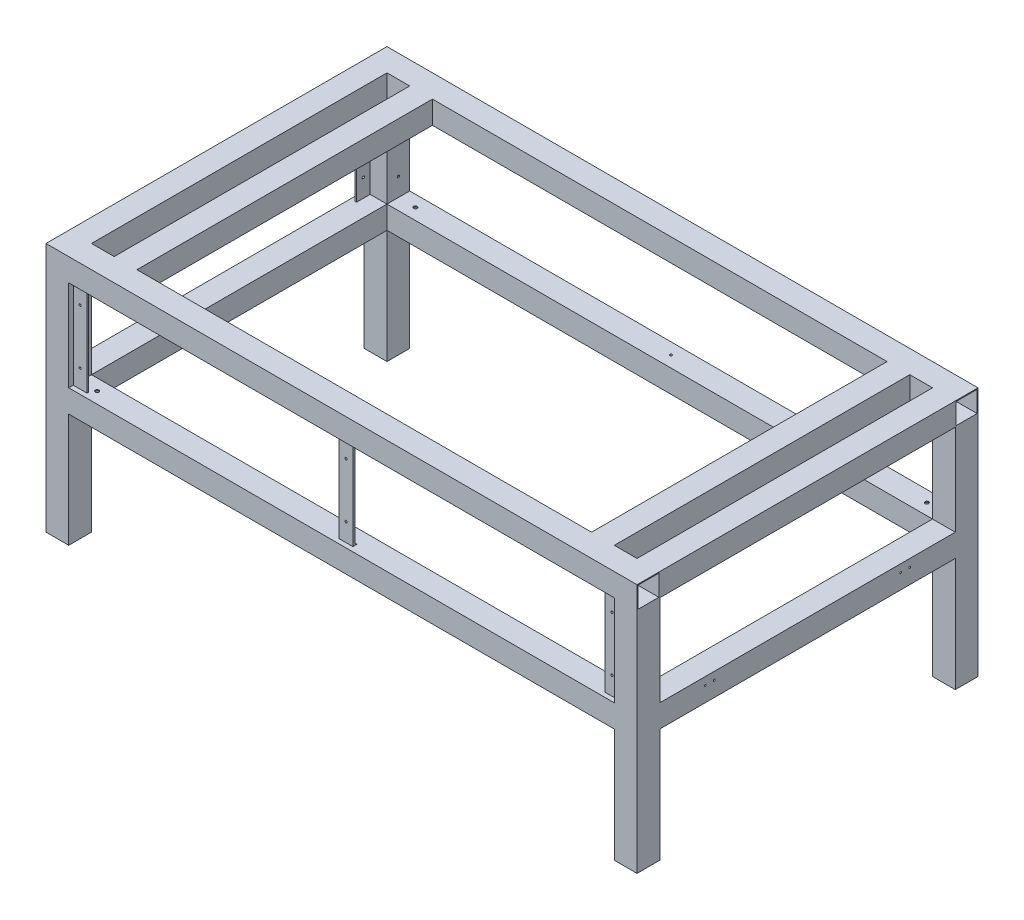
SolidWorks part; units mm, degrees
ref_plane "Plan de face" through (0, 0, 0) normal (0, 0, 1) x (1, 0, 0)
ref_plane "Plan de dessus" through (0, 0, 0) normal (0, 1, 0) x (1, 0, 0)
ref_plane "Plan de droite" through (0, 0, 0) normal (1, 0, 0) x (0, 0, -1)
sketch "Esquisse1" plane through (0, 0, 0) normal (0, 1, 0) x (1, 0, 0)
  line L1 (0, 0) -> (1300, 0)
  line L2 (0, 0) -> (0, 750)
  line L3 (0, 750) -> (1300, 750)
  line L4 (1300, 0) -> (1300, 750)
  line L5 (50, 700) -> (1250, 700)
  line L6 (50, 700) -> (50, 50)
  line L7 (50, 50) -> (1250, 50)
  line L8 (1250, 700) -> (1250, 50)
  dimension "D1" = 1300
  dimension "D2" = 750
  dimension "D3" = 50
  dimension "D4" = 50
  dimension "D5" = 50
  dimension "D6" = 50
extrude "Boss.-Extru.1" add sketch "Esquisse1" against normal blind 550
sketch "Esquisse2" plane through (0, 0, 0) normal (0, 0, 1) x (1, 0, 0)
  line L0 (0, 0) -> (1300, 0) construction
  line L1 (50, -50) -> (1250, -50)
  line L2 (50, -50) -> (50, -250)
  line L3 (50, -250) -> (1250, -250)
  line L4 (1250, -50) -> (1250, -250)
  line L5 (50, -300) -> (1250, -300)
  line L6 (50, -300) -> (50, -550)
  line L7 (50, -550) -> (1250, -550)
  line L8 (1250, -300) -> (1250, -550)
  line L9 (0, -550) -> (1300, -550) construction
  line L10 (1300, -550) -> (1300, 0) construction
  line L11 (0, -550) -> (0, 0) construction
  point P12 (1250, -425)
  dimension "D1" = 50
  dimension "D2" = 50
  dimension "D3" = 200
  dimension "D4" = 0
  dimension "D5" = 50
  dimension "D6" = 50
  dimension "D7" = 50
  dimension "D8" = 50
extrude "Enlèv. mat.-Extru.1" cut sketch "Esquisse2" against normal through all
sketch "Esquisse3" plane through (0, 0, 0) normal (-1, 0, 0) x (0, 0, 1)
  line L0 (-750, -550) -> (0, -550) construction
  line L1 (-700, -50) -> (-50, -50)
  line L2 (-700, -50) -> (-700, -250)
  line L3 (-700, -250) -> (-50, -250)
  line L4 (-50, -50) -> (-50, -250)
  line L5 (-700, -300) -> (-50, -300)
  line L6 (-700, -300) -> (-700, -550)
  line L7 (-700, -550) -> (-50, -550)
  line L8 (-50, -300) -> (-50, -550)
  line L9 (-750, 0) -> (0, 0) construction
  line L10 (0, -550) -> (0, 0) construction
  line L11 (-750, -550) -> (-750, 0) construction
  dimension "D1" = 50
  dimension "D2" = 50
  dimension "D3" = 50
  dimension "D4" = 50
  dimension "D5" = 50
  dimension "D6" = 200
  dimension "D7" = 50
extrude "Enlèv. mat.-Extru.2" cut sketch "Esquisse3" against normal through all
sketch "Esquisse4" plane through (0, 0, 0) normal (0, 1, 0) x (1, 0, 0)
  line L0 (1250, 700) -> (50, 700) construction
  line L1 (100, 700) -> (150, 700)
  line L2 (100, 700) -> (100, 50)
  line L3 (100, 50) -> (150, 50)
  line L4 (150, 700) -> (150, 50)
  line L5 (50, 50) -> (1250, 50) construction
  line L6 (50, 700) -> (50, 50) construction
  line L7 (1150, 700) -> (1200, 700)
  line L8 (1150, 700) -> (1150, 50)
  line L9 (1150, 50) -> (1200, 50)
  line L10 (1200, 700) -> (1200, 50)
  line L11 (1250, 50) -> (1250, 700) construction
  dimension "D1" = 50
  dimension "D2" = 50
  dimension "D3" = 50
  dimension "D4" = 50
extrude "Boss.-Extru.2" add sketch "Esquisse4" against normal blind 50 separate body
sketch "Esquisse18" plane through (0, -250, 0) normal (0, 1, 0) x (1, 0, 0)
  line L0 (50, 0) -> (1250, 0) construction
  line L1 (50, 750) -> (1250, 750) construction
  line L2 (1250, 750) -> (1250, 700) construction
  line L3 (50, 750) -> (50, 700) construction
  line L4 (1250, 50) -> (1250, 0) construction
  line L5 (50, 50) -> (50, 0) construction
  circle A0 centre (1212.5, 25) radius 4
  circle A1 centre (87.5, 25) radius 4
  circle A2 centre (87.5, 725) radius 4
  circle A3 centre (1212.5, 725) radius 4
  dimension "D1" = 8
  dimension "D2" = 8
  dimension "D3" = 8
  dimension "D4" = 8
  dimension "D5" = 1125
  dimension "D6" = 1125
  dimension "D7" = 25
  dimension "D8" = 25
  dimension "D9" = 25
  dimension "D10" = 25
  dimension "D11" = 700
  dimension "D12" = 700
  dimension "D13" = 37.5
  dimension "D14" = 37.5
  dimension "D15" = 37.5
  dimension "D16" = 37.5
extrude "Enlèv. mat.-Extru.5" cut sketch "Esquisse18" against normal blind 80
sketch "Esquisse19" plane through (0, -300, 0) normal (0, -1, 0) x (-1, 0, 0)
  circle A0 centre (-1212.5, 725) radius 15
  circle A1 centre (-87.5, 725) radius 15
  circle A2 centre (-87.5, 25) radius 15
  circle A3 centre (-1212.5, 25) radius 15
  dimension "D1" = 30
  dimension "D2" = 30
  dimension "D3" = 30
  dimension "D4" = 30
extrude "Enlèv. mat.-Extru.6" cut sketch "Esquisse19" against normal blind 48
sketch "Esquisse20" plane through (0, 0, 0) normal (-1, 0, 0) x (0, 0, 1)
  line L0 (-750, 0) -> (0, 0) construction
  line L1 (-2, -2) -> (-48, -2)
  line L2 (-2, -2) -> (-2, -48)
  line L3 (-2, -48) -> (-48, -48)
  line L4 (-48, -2) -> (-48, -48)
  line L5 (-702, -2) -> (-748, -2)
  line L6 (-702, -2) -> (-702, -48)
  line L7 (-702, -48) -> (-748, -48)
  line L8 (-748, -2) -> (-748, -48)
  line L9 (-750, -550) -> (-750, 0) construction
  line L10 (0, -550) -> (0, 0) construction
  dimension "D1" = 2
  dimension "D2" = 2
  dimension "D3" = 46
  dimension "D4" = 46
  dimension "D5" = 2
  dimension "D6" = 46
  dimension "D7" = 46
  dimension "D8" = 2
extrude "Enlèv. mat.-Extru.7" cut sketch "Esquisse20" against normal blind 10000
sketch "Esquisse21" plane through (0, -550, 0) normal (0, -1, 0) x (-1, 0, 0)
  line L0 (0, 0) -> (-50, 0) construction
  line L1 (-1252, 2) -> (-1298, 2)
  line L2 (-1252, 2) -> (-1252, 48)
  line L3 (-1252, 48) -> (-1298, 48)
  line L4 (-1298, 2) -> (-1298, 48)
  line L5 (-1252, 702) -> (-1298, 702)
  line L6 (-1252, 702) -> (-1252, 748)
  line L7 (-1252, 748) -> (-1298, 748)
  line L8 (-1298, 702) -> (-1298, 748)
  line L9 (-2, 702) -> (-48, 702)
  line L10 (-2, 702) -> (-2, 748)
  line L11 (-2, 748) -> (-48, 748)
  line L12 (-48, 702) -> (-48, 748)
  line L13 (-2, 2) -> (-48, 2)
  line L14 (-2, 2) -> (-2, 48)
  line L15 (-2, 48) -> (-48, 48)
  line L16 (-48, 2) -> (-48, 48)
  line L17 (-50, 50) -> (-50, 0) construction
  line L18 (-50, 50) -> (0, 50) construction
  line L19 (-50, 700) -> (0, 700) construction
  line L20 (-50, 750) -> (-50, 700) construction
  line L21 (-1300, 700) -> (-1250, 700) construction
  line L22 (-1300, 700) -> (-1300, 750) construction
  line L23 (-1250, 0) -> (-1300, 0) construction
  line L24 (-1300, 0) -> (-1300, 50) construction
  dimension "D1" = 46
  dimension "D2" = 2
  dimension "D3" = 2
  dimension "D4" = 2
  dimension "D5" = 46
  dimension "D6" = 46
  dimension "D7" = 2
  dimension "D8" = 2
  dimension "D9" = 46
  dimension "D10" = 46
  dimension "D11" = 2
  dimension "D12" = 2
  dimension "D13" = 46
  dimension "D14" = 46
  dimension "D15" = 2
  dimension "D16" = 2
extrude "Enlèv. mat.-Extru.8" cut sketch "Esquisse21" against normal blind 500
sketch "Esquisse22" plane through (0, 0, -50) normal (0, 0, -1) x (-1, 0, 0)
  line L0 (-50, -50) -> (0, -50) construction
  line L1 (-10, -50) -> (-40, -50)
  line L2 (-10, -50) -> (-10, -250)
  line L3 (-10, -250) -> (-40, -250)
  line L4 (-40, -50) -> (-40, -250)
  line L5 (-50, -250) -> (0, -250) construction
  line L6 (0, -250) -> (0, -50) construction
  dimension "D1" = 30
  dimension "D2" = 10
extrude "Boss.-Extru.11" add sketch "Esquisse22" along normal blind 3
sketch "Esquisse23" plane through (10, 0, 0) normal (-1, 0, 0) x (0, 0, 1)
  line L2 (-50, -250) -> (-80, -250)
  line L3 (-50, -250) -> (-50, -50)
  line L4 (-50, -50) -> (-80, -50)
  line L5 (-80, -250) -> (-80, -50)
  line L6 (-53, -50) -> (-50, -50) construction
  circle A0 centre (-65, -90) radius 2.5
  circle A1 centre (-65, -210) radius 2.5
  dimension "D2" = 5
  dimension "D3" = 5
  dimension "D1" = 30
  dimension "D4" = 0
  dimension "D5" = 15
  dimension "D6" = 15
  dimension "D7" = 40
  dimension "D8" = 40
extrude "Boss.-Extru.12" add sketch "Esquisse23" against normal blind 3
ref_plane "Plan1" through (0, 0, -375) normal (0, 0, 1) x (1, 0, 0)
ref_plane "Plan2" through (650, 0, 0) normal (-1, 0, 0) x (0, 0, 1)
ref_plane "Plan4" through (137.5, 0, 137.5) normal (0.7071, 0, 0.7071) x (0.7071, 0, -0.7071)
ref_plane "Plan5" through (0, 0, 0) normal (-0.7071, 0, -0.7071) x (-0.7071, 0, 0.7071)
mirror "Symétrie3" about plane through (0, 0, 0) normal (-0.7071, 0, -0.7071) of "Boss.-Extru.11", "Boss.-Extru.12"
sketch "Esquisse25" plane through (0, 0, -50) normal (0, 0, -1) x (-1, 0, 0)
  line L0 (-150, -50) -> (-150, 0) construction
  line L1 (-150, -5) -> (-1150, -5)
  line L2 (-150, -5) -> (-150, -25)
  line L3 (-150, -25) -> (-1150, -25)
  line L4 (-1150, -5) -> (-1150, -25)
  line L5 (-1150, -50) -> (-1150, 0) construction
  line L6 (-50, 0) -> (-1250, 0) construction
  dimension "D1" = 5
  dimension "D2" = 20
extrude "Boss.-Extru.14" add sketch "Esquisse25" along normal blind 3
sketch "Esquisse29" plane through (1250, 0, 0) normal (-1, 0, 0) x (0, 0, 1)
  line L0 (-750, -250) -> (-750, -50) construction
  line L1 (-750, -50) -> (-700, -50) construction
  line L2 (-750, -250) -> (-700, -250) construction
  circle A0 centre (-725, -210) radius 2.5
  circle A1 centre (-725, -90) radius 2.5
  dimension "D1" = 5
  dimension "D2" = 5
  dimension "D3" = 25
  dimension "D4" = 25
  dimension "D5" = 40
  dimension "D6" = 40
extrude "Enlèv. mat.-Extru.9" cut sketch "Esquisse29" against normal blind 10
mirror "Symétrie9" about plane through (650, 0, 0) normal (-1, 0, 0) of "Enlèv. mat.-Extru.9"
sketch "Esquisse30" plane through (0, -250, 0) normal (0, 1, 0) x (1, 0, 0)
  line L1 (50, 750) -> (1250, 750) construction
  line L2 (650, 302.5) -> (650, -302.5) construction
  circle A0 centre (650, 725) radius 2.5
  dimension "D1" = 5
  dimension "D2" = 25
  dimension "D3" = 0
extrude "Enlèv. mat.-Extru.10" cut sketch "Esquisse30" against normal blind 15
ref_plane "Plan6" through (0, -150, 0) normal (0, -1, 0) x (-1, 0, 0)
mirror "Symétrie10" about plane through (0, -150, 0) normal (0, -1, 0) of "Enlèv. mat.-Extru.10"
sketch "Esquisse31" plane through (0, -250, 0) normal (0, 1, 0) x (1, 0, 0)
  line L0 (50, 0) -> (1250, 0) construction
  line L1 (635, 15) -> (665, 15)
  line L2 (635, 15) -> (635, 10)
  line L3 (635, 10) -> (665, 10)
  line L4 (665, 15) -> (665, 10)
  line L5 (650, 302.5) -> (650, -302.5) construction
  point P6 (650, 10)
  dimension "D1" = 5
  dimension "D2" = 10
  dimension "D3" = 0
  dimension "D4" = 30
extrude "Boss.-Extru.18" add sketch "Esquisse31" along normal blind 200
fillet "Congé1" radius 5 2 edges at (650, -250, -15) (650, -50, -15)
sketch "Esquisse32" plane through (0, 0, -10) normal (0, 0, 1) x (1, 0, 0)
  line L0 (635, -250) -> (665, -250) construction
  line L1 (635, -50) -> (665, -50) construction
  line L2 (635, -50) -> (635, -250) construction
  circle A0 centre (650, -210) radius 2.5
  circle A1 centre (650, -90) radius 2.5
  dimension "D1" = 5
  dimension "D2" = 5
  dimension "D3" = 40
  dimension "D4" = 40
  dimension "D5" = 15
  dimension "D6" = 15
extrude "Enlèv. mat.-Extru.11" cut sketch "Esquisse32" against normal blind 5
mirror "Symétrie11" about plane through (0, 0, -375) normal (0, 0, 1) of "Boss.-Extru.12"
mirror "Symétrie15" about plane through (650, 0, 0) normal (-1, 0, 0) of "Symétrie3"
sketch "Esquisse33" plane through (1300, 0, 0) normal (1, 0, 0) x (0, 0, -1)
  line L0 (50, -50) -> (700, -50) construction
  line L1 (50, -250) -> (130.649, -250)
  line L2 (50, -250) -> (50, -50)
  line L3 (50, -50) -> (130.649, -50)
  line L4 (130.649, -250) -> (130.649, -50)
extrude "Enlèv. mat.-Extru.12" cut sketch "Esquisse33" against normal blind 78
sketch "Esquisse34" plane through (1300, 0, 0) normal (1, 0, 0) x (0, 0, -1)
  line L0 (50, -250) -> (50, -50) construction
  line L1 (700, -250) -> (50, -250) construction
  circle A0 centre (150, -267) radius 2
  circle A1 centre (170, -267) radius 2
  dimension "D2" = 4
  dimension "D3" = 4
  dimension "D1" = 20
  dimension "D4" = 100
  dimension "D5" = 17
  dimension "D6" = 17
extrude "Enlèv. mat.-Extru.13" cut sketch "Esquisse34" against normal blind 25
mirror "Symétrie16" about plane through (0, 0, -375) normal (0, 0, 1) of "Enlèv. mat.-Extru.13"
